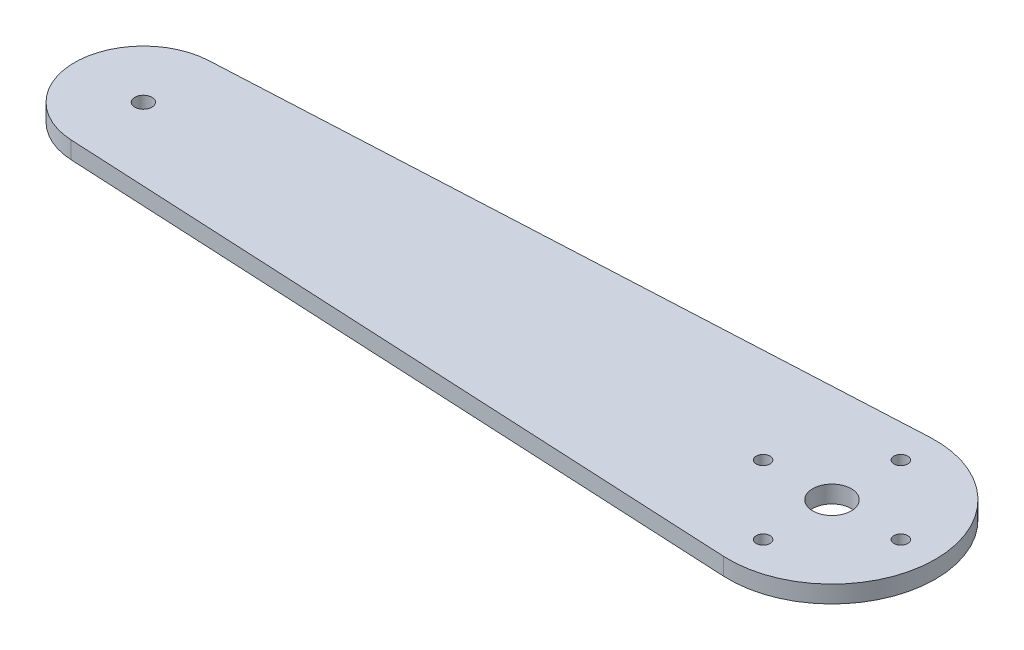
SolidWorks part; units mm, degrees
ref_plane "Front Plane" through (0, 0, 0) normal (0, 0, 1) x (1, 0, 0)
ref_plane "Top Plane" through (0, 0, 0) normal (0, 1, 0) x (1, 0, 0)
ref_plane "Right Plane" through (0, 0, 0) normal (1, 0, 0) x (0, 0, -1)
sketch "Sketch1" plane through (0, 0, 0) normal (0, 1, 0) x (1, 0, 0)
  line L0 (-127.635, 12.6841) -> (-0.9525, 19.0262)
  line L1 (-127.635, -12.6841) -> (-0.9525, -19.0262)
  line L2 (-111.3601, 0) -> (-50111.3601, 0) construction
  line L3 (0, -984.3615) -> (0, 49015.6385) construction
  line L4 (0, 0) -> (0, 12.7) construction
  line L5 (0, 0) -> (12.7, 0) construction
  arc A0 (-0.9525, -19.0262) -> (-0.9525, 19.0262) centre (0, 0) ccw
  arc A1 (-127.635, 12.6841) -> (-127.635, -12.6841) centre (-127, 0) ccw
  circle A2 centre (-127, 0) radius 1.5875
  circle A3 centre (0, 0) radius 3.556
  circle A4 centre (0, 12.7) radius 1.27
  circle A5 centre (12.7, 0) radius 1.27
  circle A6 centre (0, -12.7) radius 1.27
  circle A7 centre (-12.7, 0) radius 1.27
  dimension "D1" = 12.7
  dimension "D2" = 19.05
  dimension "D4" = 3.175
  dimension "D5" = 7.112
  dimension "D6" = 2.54
  dimension "D3" = 127
  dimension "D7" = 12.7
  dimension "D9" = 90
  dimension "D10" = 12.7
  dimension "D8" = 4
extrude "Boss-Extrude1" add sketch "Sketch1" along normal blind 3.175
